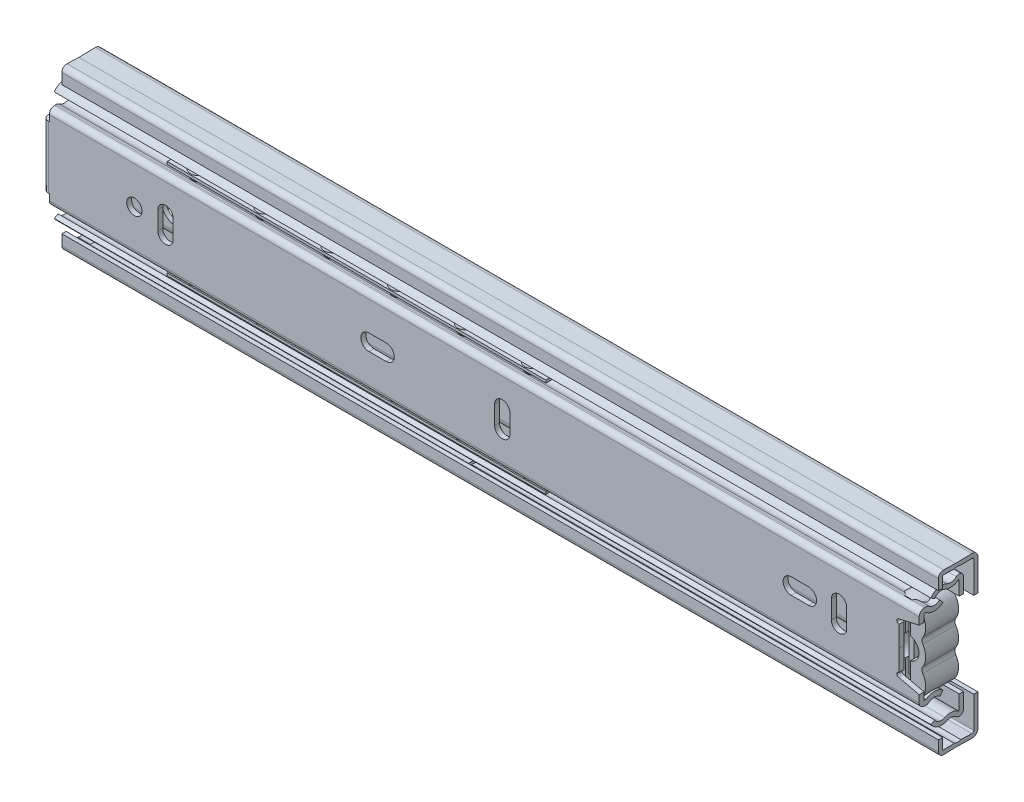
SolidWorks part; units mm, degrees
ref_plane "Front" through (0, 0, 0) normal (0, 0, 1) x (1, 0, 0)
ref_plane "Top" through (0, 0, 0) normal (0, 1, 0) x (1, 0, 0)
ref_plane "Right" through (0, 0, 0) normal (1, 0, 0) x (0, 0, -1)
sketch "Sketch1" plane through (0, 0, 0) normal (1, 0, 0) x (0, 0, -1)
  line L1 (5.6388, 0) -> (-5.6388, 0) construction
  line L4 (-4.1393, 22.8203) -> (-0.7433, 22.6989)
  line L5 (-1.1312, 21.5182) -> (-4.1819, 21.6273)
  line L6 (-4.445, 18.415) -> (-5.6388, 18.415)
  line L7 (-4.445, 21.3734) -> (-4.445, 18.415)
  line L8 (-5.6388, 18.415) -> (-5.6388, 21.3734)
  line L9 (3.9237, 21.6269) -> (0.7619, 21.5441)
  line L10 (5.6388, 0) -> (5.6388, 21.1191)
  line L11 (4.445, 21.1191) -> (4.445, 0)
  line L12 (5.6388, 0) -> (4.445, 0)
  line L13 (-0.7433, 22.6989) -> (3.8925, 22.8203)
  arc A0 (-4.445, 21.3734) -> (-4.1819, 21.6273) centre (-4.191, 21.3734) cw
  arc A1 (-5.6388, 21.3734) -> (-4.1393, 22.8203) centre (-4.191, 21.3734) cw
  arc A3 (3.9237, 21.6269) -> (4.445, 21.1191) centre (3.937, 21.1191) cw
  arc A4 (3.8925, 22.8203) -> (5.6388, 21.1191) centre (3.937, 21.1191) cw
  arc A5 (-1.1312, 21.5182) -> (0.7619, 21.5441) centre (-0.1524, 19.1744) cw
  dimension "D2" = 19.1744
  dimension "D7" = 0.254
  dimension "D8" = 0.508
  dimension "D6" = 2.54
  dimension "D9" = 1.1938
  dimension "D10" = 88.5
  dimension "D1" = 11.2776
  dimension "D3" = 5.7912
  dimension "D4" = 36.83
  dimension "D5" = 1.1938
  dimension "D11" = 87.953
  dimension "D12" = 45.6406
extrude "Extrude1" add sketch "Sketch1" along normal mid plane 249.936
ref_plane "Travel / 2" through (-127, 0, 0) normal (-1, 0, 0) x (0, 0, 1)
sketch "Sketch2" plane through (-127, 0, 0) normal (-1, 0, 0) x (0, 0, 1)
  line L0 (0.0254, 6.1159) -> (0.0254, 0)
  line L2 (-5.6388, 0) -> (5.6388, 0) construction
  line L3 (5.6388, 21.3734) -> (5.6388, 18.415) construction
  line L7 (-4.445, 21.1191) -> (-4.445, 0) construction
  line L8 (-5.6388, 0) -> (-5.6388, 21.1191) construction
  line L13 (-3.5306, 16.3766) -> (-3.5306, 9.5217)
  line L46 (-2.3867, 7.7262) -> (-0.4146, 6.8065)
  arc A0 (0.0254, 6.1159) -> (-0.4146, 6.8065) centre (-0.7366, 6.1159) ccw
  arc A1 (-1.5056, 17.2916) -> (1.2415, 16.9143) centre (0.1524, 19.1744) ccw
  arc A4 (1.1312, 21.5182) -> (-0.7619, 21.5441) centre (0.1524, 19.1744) ccw construction
  arc A19 (-3.5306, 9.5217) -> (-2.3867, 7.7262) centre (-1.5494, 9.5217) ccw
  arc A25 (-1.5056, 17.2916) -> (-3.5306, 16.3766) centre (-2.3114, 16.3766) ccw
  arc A51 (5.7404, 15.6277) -> (1.2415, 16.9143) centre (2.7686, 13.7451) ccw
  dimension "D2" = 8.4074
  dimension "D3" = 27.4903
  dimension "D6" = 1.9812
  dimension "D8" = 12.2319
  dimension "D10" = 2.5088
  dimension "D11" = 1.2192
  dimension "D4" = 0.762
  dimension "D5" = 4.4704
  dimension "D7" = 115
  dimension "D9" = 19.0435
  dimension "D13" = 11.3792
extrude "Middle Member" add sketch "Sketch2" against normal blind 249.936 separate body thin thin type one direction reverse wall 1.2192
ref_plane "Travel" through (-129.032, 0, 0) normal (-1, 0, 0) x (0, 0, 1)
sketch "Sketch3" plane through (-129.032, 0, 0) normal (-1, 0, 0) x (0, 0, 1)
  line L0 (1.2446, 0) -> (0.0254, 0) construction
  line L1 (-5.6388, 0) -> (-5.6388, 21.1191) construction
  line L56 (7.0612, 0) -> (7.0612, 10.6235)
  line L93 (5.5372, 12.1475) -> (5.1643, 12.1475)
  arc A0 (1.2082, 11.9072) -> (4.2365, 11.8325) centre (2.7686, 13.7451) ccw
  arc A29 (7.0612, 10.6235) -> (5.5372, 12.1475) centre (5.5372, 10.6235) ccw
  arc A53 (5.1643, 12.1475) -> (4.2365, 11.8325) centre (5.1643, 10.6235) ccw
  dimension "D1" = 1.524
  dimension "D4" = 1.524
  dimension "D5" = 2.411
  dimension "D2" = 12.7
  dimension "D3" = 12.1475
  dimension "D6" = 5.853
extrude "Drawer Member" add sketch "Sketch3" against normal blind 249.936 thin thin type one direction wall 1.397
sketch "Sketch6" plane through (0, 0, 7.0612) normal (0, 0, 1) x (1, 0, 0)
  line L1 (-129.032, 0) -> (-127.127, 0)
  line L2 (-129.032, 0) -> (-129.032, 12.1475)
  line L3 (-129.032, 12.1475) -> (-127.127, 12.1475)
  line L4 (-127.127, 0) -> (-127.127, 12.1475)
  line L5 (120.904, 12.1475) -> (-129.032, 12.1475) construction
  line L7 (-129.032, 10.6235) -> (-129.032, 0) construction
  line L8 (120.904, 0) -> (-129.032, 0) construction
  dimension "D1" = 1.905
extrude "Cut-Extrude1" cut sketch "Sketch6" against normal through all
sketch "Sketch7" plane through (0, 0, 0) normal (0, -1, 0) x (1, 0, 0)
  line L0 (-127.127, 7.0612) -> (-127.381, 7.0612)
  line L1 (-129.032, 5.4102) -> (-129.032, 0.3041)
  line L2 (-129.032, 0.3041) -> (-127.635, 0.3041)
  line L3 (-127.635, 0.3041) -> (-127.635, 5.4102)
  line L4 (-127.381, 5.6642) -> (-127.127, 5.6642)
  line L5 (120.904, 5.6642) -> (-127.127, 5.6642) construction
  line L6 (-127.127, 7.0612) -> (-127.127, 5.6642)
  line L7 (120.904, 0.3041) -> (-127.127, 0.3041) construction
  line L9 (-127.127, 5.087) -> (-127.127, 0.3041) construction
  arc A0 (-127.381, 5.6642) -> (-127.635, 5.4102) centre (-127.381, 5.4102) ccw
  arc A1 (-127.381, 7.0612) -> (-129.032, 5.4102) centre (-127.381, 5.4102) ccw
  dimension "D1" = 0.254
  dimension "D2" = 1.905
extrude "Extrude4" add sketch "Sketch7" against normal blind 8.89
sketch "Sketch8" plane through (0, 0, -4.445) normal (0, 0, 1) x (1, 0, 0)
  line L0 (115.3295, 7.6456) -> (116.7638, 7.493)
  line L1 (124.968, 12.2048) -> (115.5714, 12.2048)
  line L2 (116.7638, 7.493) -> (116.7638, 0)
  line L3 (124.968, 0) -> (-124.968, 0) construction
  line L4 (124.968, 21.1191) -> (124.968, 0) construction
  line L5 (124.968, 12.2048) -> (124.968, 0)
  line L6 (124.968, 0) -> (116.7638, 0)
  arc A0 (115.5714, 12.2048) -> (115.3295, 7.6456) centre (115.5714, 9.9188) ccw
  dimension "D3" = 9.9188
  dimension "D1" = 12.2048
  dimension "D2" = 8.2042
  dimension "D4" = 9.3966
  dimension "D5" = 7.493
extrude "Cut-Extrude2" cut sketch "Sketch8" against normal up to next (1.1938 mm away)
sketch "Sketch9" plane through (0, 0, -4.445) normal (0, 0, 1) x (1, 0, 0)
  line L0 (116.7638, 0) -> (-124.968, 0) construction
  line L1 (116.7638, 7.493) -> (115.3668, 7.493)
  line L2 (116.7638, 7.493) -> (116.7638, 0)
  line L3 (116.7638, 0) -> (115.3668, 0)
  line L4 (115.3668, 7.493) -> (115.3668, 0)
  dimension "D1" = 1.397
extrude "Extrude5" add sketch "Sketch9" along normal up to surface (8.89 mm away) up to face at (0, 19.8942, 4.445)
sketch "Sketch10" plane through (0, 0, 4.445) normal (0, 0, 1) x (1, 0, 0)
  line L0 (110.9853, 0) -> (112.8903, 0)
  line L1 (115.3509, 9.8425) -> (116.7797, 9.8425)
  line L2 (115.3509, 3.0936) -> (115.3509, 9.8425)
  line L3 (116.7797, 3.0936) -> (116.7797, 9.8425)
  line L6 (119.2403, 0) -> (121.1453, 0)
  line L7 (115.3668, 0) -> (-124.968, 0) construction
  line L8 (116.0653, 0) -> (116.0653, 4.4715) construction
  line L9 (115.3668, 0) -> (116.7638, 0) construction
  arc A0 (121.1453, 0) -> (120.3355, 2.7517) centre (116.0653, 0) ccw
  arc A1 (120.3355, 4.4715) -> (120.3355, 2.7517) centre (121.67, 3.6116) ccw
  arc A2 (120.3355, 4.4715) -> (111.7951, 4.4715) centre (116.0653, 7.2231) ccw
  arc A3 (111.7951, 2.7517) -> (111.7951, 4.4715) centre (110.4606, 3.6116) ccw
  arc A4 (111.7951, 2.7517) -> (110.9853, 0) centre (116.0653, 0) ccw
  arc A5 (115.3509, 3.0936) -> (112.8903, 0) centre (116.0653, 0) ccw
  arc A6 (119.2403, 0) -> (116.7797, 3.0936) centre (116.0653, 0) ccw
  dimension "D1" = 3.175
  dimension "D2" = 5.08
  dimension "D5" = 5.08
  dimension "D6" = 1.5875
  dimension "D3" = 9.8425
  dimension "D4" = 1.4288
  dimension "D7" = 7.2231
extrude "Extrude6" add sketch "Sketch10" along normal blind 1.016 and the other way offset from surface 0.508 separate body other way up to face at (64.0263, 9.9327, -4.445)
sketch "Sketch11" plane through (0, 0, 7.0612) normal (0, 0, 1) x (1, 0, 0)
  line L0 (115.189, 5.9678) -> (115.189, 0)
  line L8 (120.904, 8.5893) -> (115.0447, 7.2212)
  line L11 (115.189, 0) -> (120.904, 0)
  line L12 (120.904, 0) -> (120.904, 8.5893)
  arc A1 (115.0447, 7.2212) -> (115.189, 5.9678) centre (115.1891, 6.6028) ccw
  dimension "D3" = 0.635
  dimension "D1" = 5.715
  dimension "D2" = 8.5893
  dimension "D4" = 5.9678
  dimension "D5" = 103.143
extrude "Cut-Extrude3" cut sketch "Sketch11" against normal up to next (1.397 mm away)
sketch "Sketch12" plane through (0, 0, 1.2446) normal (0, 0, 1) x (1, 0, 0)
  line L0 (122.936, 12.065) -> (112.776, 12.065)
  line L1 (122.936, 16.3766) -> (122.936, 9.5217) construction
  line L2 (110.236, 9.525) -> (110.236, 0)
  line L3 (122.936, 0) -> (-127, 0) construction
  line L4 (110.236, 0) -> (122.936, 0)
  line L5 (122.936, 0) -> (122.936, 12.065)
  arc A0 (112.776, 12.065) -> (110.236, 9.525) centre (112.776, 9.525) ccw
  point P11 (110.236, 12.065)
  dimension "D3" = 2.54
  dimension "D1" = 12.7
  dimension "D2" = 12.065
extrude "Cut-Extrude4" cut sketch "Sketch12" against normal through all
sketch "Sketch13" plane through (0, 0, -4.445) normal (0, 0, 1) x (1, 0, 0)
  line L0 (-56.5797, 7.112) -> (-81.4082, 7.112)
  line L1 (115.3668, 0) -> (-124.968, 0) construction
  line L2 (-64.6696, 0) -> (-64.6696, 4.2392) construction
  line L3 (-107.5067, 10.287) -> (-56.5797, 10.287)
  line L4 (-124.968, 21.1191) -> (-124.968, 0) construction
  line L5 (-85.2182, 7.112) -> (-107.5067, 7.112)
  line L6 (-84.4562, 0) -> (-84.4562, 6.35)
  line L7 (-82.1702, 6.35) -> (-82.1702, 0)
  line L8 (-62.1931, 2.286) -> (-67.1461, 2.286)
  line L13 (-101.2456, 0) -> (-96.6736, 0)
  line L14 (-93.143, 0) -> (-86.793, 0)
  line L15 (-84.4562, 0) -> (-82.1702, 0)
  line L16 (-79.6556, 0) -> (-75.0836, 0)
  line L17 (-69.4321, 0) -> (-59.9071, 0)
  arc A1 (-107.5067, 10.287) -> (-107.5067, 7.112) centre (-107.5067, 8.6995) ccw
  arc A2 (-84.4562, 6.35) -> (-85.2182, 7.112) centre (-85.2182, 6.35) ccw
  arc A4 (-81.4082, 7.112) -> (-82.1702, 6.35) centre (-81.4082, 6.35) ccw
  arc A7 (-56.5797, 7.112) -> (-56.5797, 10.287) centre (-56.5797, 8.6995) ccw
  arc A8 (-86.793, 0) -> (-93.143, 0) centre (-89.968, 0) ccw
  arc A9 (-96.6736, 0) -> (-101.2456, 0) centre (-98.9596, 0) ccw
  arc A10 (-75.0836, 0) -> (-79.6556, 0) centre (-77.3696, 0) ccw
  arc A11 (-59.9071, 0) -> (-62.1931, 2.286) centre (-62.1931, 0) ccw
  arc A12 (-67.1461, 2.286) -> (-69.4321, 0) centre (-67.1461, 0) ccw
  dimension "D3" = 2.286
  dimension "D4" = 3.175
  dimension "D7" = 8.9916
  dimension "D8" = 21.59
  dimension "D9" = 34.29
  dimension "D10" = 0.762
  dimension "D11" = 17.5387
  dimension "D12" = 9.525
  dimension "D13" = 5.5118
  dimension "D14" = 35
  dimension "D1" = 3.175
  dimension "D2" = 50.927
  dimension "D5" = 2.286
  dimension "D6" = 10.287
extrude "Cut-Extrude5" cut sketch "Sketch13" against normal up to next (1.1938 mm away)
sketch "Sketch32" plane through (0, 0, -5.6388) normal (0, 0, -1) x (-1, 0, 0)
  line L0 (-55.4945, 0) -> (-45.9695, 0)
  line L1 (-41.207, 0) -> (-34.857, 0)
  line L2 (-31.3645, 0) -> (-21.8395, 0)
  line L3 (-18.474, 0) -> (-13.902, 0)
  line L4 (-116.7638, 0) -> (59.9071, 0) construction
  line L5 (107.5067, 10.287) -> (56.5797, 10.287) construction
  line L6 (56.5797, 7.112) -> (81.4082, 7.112) construction
  line L7 (-26.602, 2.286) -> (-26.602, -3.4269) construction
  line L8 (-50.732, 2.286) -> (-50.732, -3.4269) construction
  line L14 (-58.6695, 10.287) -> (-15.426, 10.287)
  line L15 (-19.998, 7.112) -> (-58.6695, 7.112)
  line L17 (-13.902, 8.763) -> (-13.902, 0)
  line L18 (-18.474, 0) -> (-18.474, 5.588)
  line L23 (-53.2085, 2.286) -> (-48.2555, 2.286)
  line L25 (-29.0785, 2.286) -> (-24.1255, 2.286)
  arc A0 (93.143, 0) -> (86.793, 0) centre (89.968, 0) ccw construction
  arc A13 (-13.902, 8.763) -> (-15.426, 10.287) centre (-15.426, 8.763) ccw
  arc A14 (-18.474, 5.588) -> (-19.998, 7.112) centre (-19.998, 5.588) ccw
  arc A17 (-58.6695, 10.287) -> (-58.6695, 7.112) centre (-58.6695, 8.6995) ccw
  arc A20 (-45.9695, 0) -> (-48.2555, 2.286) centre (-48.2555, 0) ccw
  arc A21 (-53.2085, 2.286) -> (-55.4945, 0) centre (-53.2085, 0) ccw
  arc A22 (-34.857, 0) -> (-41.207, 0) centre (-38.032, 0) ccw
  arc A24 (-21.8395, 0) -> (-24.1255, 2.286) centre (-24.1255, 0) ccw
  arc A25 (-29.0785, 2.286) -> (-31.3645, 0) centre (-29.0785, 0) ccw
  dimension "D2" = 1.524
  dimension "D3" = 3.175
  dimension "D4" = 9.525
  dimension "D5" = 2.286
  dimension "D6" = 11.43
  dimension "D7" = 12.7
  dimension "D8" = 24.13
  dimension "D9" = 20.6375
  dimension "D10" = 128
  dimension "D1" = 4.572
extrude "Cut-Extrude14" cut sketch "Sketch32" against normal up to next (1.1938 mm away)
sketch "Sketch31" plane through (0, 0, -5.6388) normal (0, 0, -1) x (-1, 0, 0)
  line L0 (-124.968, 12.2048) -> (-124.968, 21.1191) construction
  line L1 (-116.7638, 0) -> (-55.4945, 0) construction
  line L2 (-109.093, 0) -> (-102.743, 0)
  arc A0 (-102.743, 0) -> (-109.093, 0) centre (-105.918, 0) ccw
  dimension "D1" = 19.05
  dimension "D2" = 6.35
extrude "Cut-Extrude15" cut sketch "Sketch31" against normal up to next (1.1938 mm away)
sketch "Sketch24" plane through (0, 0, 7.0612) normal (0, 0, 1) x (1, 0, 0)
  line L0 (115.189, 0) -> (-127.381, 0) construction
  line L1 (-93.98, 4.826) -> (-93.98, 0) construction
  line L2 (-96.1644, 2.6416) -> (-96.1644, 0)
  line L3 (-96.1644, 0) -> (-91.7956, 0)
  line L4 (-91.7956, 0) -> (-91.7956, 2.6416)
  line L5 (-38.2905, 0) -> (-28.7655, 0)
  line L6 (-36.0045, 2.286) -> (-31.0515, 2.286)
  line L8 (-0.1524, 2.6416) -> (-0.1524, 0)
  line L9 (-0.1524, 0) -> (4.2164, 0)
  line L10 (4.2164, 0) -> (4.2164, 2.6416)
  line L11 (-129.032, 8.89) -> (-129.032, 0) construction
  line L12 (-33.528, 2.286) -> (-33.528, 0) construction
  circle A0 centre (-102.87, 0) radius 2.1844
  arc A1 (-96.1644, 2.6416) -> (-91.7956, 2.6416) centre (-93.98, 2.6416) cw
  arc A2 (-38.2905, 0) -> (-36.0045, 2.286) centre (-36.0045, 0) cw
  arc A3 (-31.0515, 2.286) -> (-28.7655, 0) centre (-31.0515, 0) cw
  arc A4 (-0.1524, 2.6416) -> (4.2164, 2.6416) centre (2.032, 2.6416) cw
  dimension "D1" = 4.3688
  dimension "D4" = 8.89
  dimension "D5" = 2.286
  dimension "D7" = 60.452
  dimension "D8" = 96.012
  dimension "D2" = 35.052
  dimension "D3" = 4.826
  dimension "D6" = 9.525
extrude "Cut-Extrude13" cut sketch "Sketch24" against normal up to next (1.397 mm away)
sketch "Sketch25" plane through (0, 0, 7.0612) normal (0, 0, 1) x (1, 0, 0)
  line L0 (95.8596, 0) -> (100.2284, 0)
  line L1 (115.189, 0) -> (4.2164, 0) construction
  line L2 (100.2284, 0) -> (100.2284, 2.6416)
  line L3 (95.8596, 2.6416) -> (95.8596, 0)
  line L4 (4.2164, 0) -> (4.2164, 2.6416) construction
  line L5 (91.6305, 0) -> (82.1055, 0)
  line L6 (-31.0515, 2.286) -> (-36.0045, 2.286) construction
  line L7 (84.3915, 2.286) -> (89.3445, 2.286)
  line L8 (86.868, 0) -> (86.868, 2.286) construction
  arc A0 (100.2284, 2.6416) -> (95.8596, 2.6416) centre (98.044, 2.6416) ccw
  arc A1 (4.2164, 2.6416) -> (-0.1524, 2.6416) centre (2.032, 2.6416) ccw construction
  arc A2 (-91.7956, 2.6416) -> (-96.1644, 2.6416) centre (-93.98, 2.6416) ccw construction
  arc A3 (84.3915, 2.286) -> (82.1055, 0) centre (84.3915, 0) ccw
  arc A4 (89.3445, 2.286) -> (91.6305, 0) centre (89.3445, 0) cw
  arc A5 (-28.7655, 0) -> (-31.0515, 2.286) centre (-31.0515, 0) ccw construction
  dimension "D1" = 192.024
  dimension "D2" = 11.176
extrude "Cut E" cut sketch "Sketch25" against normal up to next (1.397 mm away)
sketch "Sketch26" plane through (0, 0, 1.2446) normal (0, 0, 1) x (1, 0, 0)
  line L0 (-101.2456, 0) -> (-59.9071, 0)
  line L1 (-96.4196, 4.826) -> (-64.7331, 4.826)
  line L2 (55.4945, 0) -> (21.8395, 0)
  line L3 (26.6655, 4.826) -> (50.6685, 4.826)
  arc A0 (-101.2456, 0) -> (-96.4196, 4.826) centre (-96.4196, 0) cw
  arc A1 (-59.9071, 0) -> (-64.7331, 4.826) centre (-64.7331, 0) ccw
  arc A2 (21.8395, 0) -> (26.6655, 4.826) centre (26.6655, 0) cw
  arc A3 (50.6685, 4.826) -> (55.4945, 0) centre (50.6685, 0) cw
  arc A5 (24.1255, 2.286) -> (21.8395, 0) centre (24.1255, 0) ccw construction
  dimension "D1" = 4.826
extrude "Cut-Extrude17" cut sketch "Sketch26" against normal up to next (1.2192 mm away)
ref_plane "Plane3" through (-112.268, 0, 0) normal (-1, 0, 0) x (0, 0, 1)
sketch "Sketch27" plane through (-112.268, 0, 0) normal (-1, 0, 0) x (0, 0, 1)
  line L0 (0.1524, 21.6832) -> (0.1524, 16.6656)
  line L1 (0.1524, 23.635) -> (0.1524, 15.2838) construction
  arc A0 (0.1524, 16.6656) -> (0.1524, 21.6832) centre (0.1524, 19.1744) ccw
  arc A1 (-1.5056, 17.2916) -> (1.2415, 16.9143) centre (0.1524, 19.1744) ccw construction
revolve "Revolve1" add sketch "Sketch27" angle 360 about L1
pattern_linear "LPattern1" count 6 spacing 19.05 along (1, 0, 0) of bodies 128
sketch "Sketch28" plane through (-112.268, 0, 0) normal (-1, 0, 0) x (0, 0, 1)
  line L0 (2.6612, 19.1744) -> (-2.3564, 19.1744) construction
  line L1 (3.9624, 18.7934) -> (-3.6576, 18.7934)
  line L2 (3.9624, 18.7934) -> (3.9624, 19.5554)
  line L3 (3.9624, 19.5554) -> (-3.6576, 19.5554)
  line L4 (-3.6576, 18.7934) -> (-3.6576, 19.5554)
  line L5 (0.1524, 20.5465) -> (0.1524, 17.804) construction
  circle A1 centre (0.1524, 19.1744) radius 2.5088 construction
  point P8 (0.1524, 19.1744)
  dimension "D1" = 7.62
  dimension "D2" = 0.762
extrude "Extrude7" add sketch "Sketch28" along normal blind 6.35 and the other way blind 101.6
ref_plane "Plane4" through (-88.9, 0, 0) normal (-1, 0, 0) x (0, 0, 1)
sketch "Sketch29" plane through (-88.9, 0, 0) normal (-1, 0, 0) x (0, 0, 1)
  line L0 (2.7686, 16.0438) -> (2.7686, 11.4464)
  line L1 (2.7686, 16.6801) -> (2.7686, 10.2973) construction
  arc A0 (2.7686, 11.4464) -> (2.7686, 16.0438) centre (2.7686, 13.7451) ccw
  arc A1 (4.7105, 14.9753) -> (1.7707, 15.816) centre (2.7686, 13.7451) ccw construction
revolve "Revolve2" add sketch "Sketch29" angle 360 about L1
pattern_linear "LPattern2" count 6 spacing 19.05 along (1, 0, 0) of bodies 135
sketch "Sketch30" plane through (-88.9, 0, 0) normal (-1, 0, 0) x (0, 0, 1)
  line L0 (0.4699, 13.7451) -> (5.0673, 13.7451) construction
  line L1 (3.9624, 18.7934) -> (3.9624, 19.5554) construction
  line L2 (0.2286, 14.1261) -> (5.3086, 14.1261)
  line L3 (0.2286, 14.1261) -> (0.2286, 13.3641)
  line L4 (0.2286, 13.3641) -> (5.3086, 13.3641)
  line L5 (5.3086, 14.1261) -> (5.3086, 13.3641)
  line L7 (2.7686, 14.2437) -> (2.7686, 12.7853) construction
  circle A0 centre (2.7686, 13.7451) radius 2.2987 construction
  point P4 (2.7686, 13.7451)
  dimension "D1" = 5.08
extrude "Extrude8" add sketch "Sketch30" along normal blind 6.35 and the other way blind 101.6
mirror "Mirror3" about plane through (0, 0, 0) normal (0, 1, 0) of bodies 117 126 163 159 124 127 119
mirror "Mirror5" about plane through (0, 0, 0) normal (0, 1, 0) of bodies 141 134
